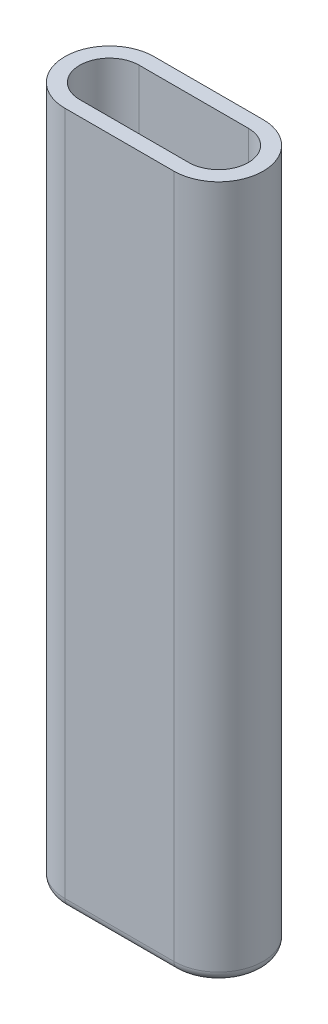
SolidWorks part; units mm, degrees
ref_plane "Płaszczyzna przednia" through (0, 0, 0) normal (0, 0, 1) x (1, 0, 0)
ref_plane "Płaszczyzna górna" through (0, 0, 0) normal (0, 1, 0) x (1, 0, 0)
ref_plane "Płaszczyzna prawa" through (0, 0, 0) normal (1, 0, 0) x (0, 0, -1)
sketch "Szkic1" plane through (0, 0, 0) normal (0, 1, 0) x (1, 0, 0)
  line L0 (-5.5, 0) -> (5.5, 0) construction
  line L1 (-5.5, 4.5) -> (5.5, 4.5)
  line L2 (-5.5, -4.5) -> (5.5, -4.5)
  arc A0 (-5.5, 4.5) -> (-5.5, -4.5) centre (-5.5, 0) ccw
  arc A1 (5.5, -4.5) -> (5.5, 4.5) centre (5.5, 0) ccw
  point P2 (0, 0)
  dimension "D3" = 20
  dimension "D1" = 9
extrude "Dodanie-wyciągnięcie1" add sketch "Szkic1" along normal blind 70
shell "Skorupa1" thickness 1.5 removed face at (0, 70, 0)
sketch "Szkic2" plane through (0, 1.5, 0) normal (0, 1, 0) x (1, 0, 0)
  line L0 (5.5, 3) -> (-5.5, 3) construction
  line L1 (-1, -3) -> (1, -3)
  line L2 (-1, -3) -> (-1, 3)
  line L3 (-1, 3) -> (1, 3)
  line L4 (1, -3) -> (1, 3)
  line L5 (-1, -3) -> (1, 3) construction
  line L6 (-1, 3) -> (1, -3) construction
  point P0 (0, 0)
  dimension "D1" = 2
extrude "Dodanie-wyciągnięcie2" add sketch "Szkic2" along normal blind 50
fillet "Zaokrąglenie2" radius 1 6 edges at (0, 0, -4.5) (10, 0, 0) (0, 0, 4.5) (-10, 0, 0) (-1, 51.5, 0) (1, 51.5, 0)
